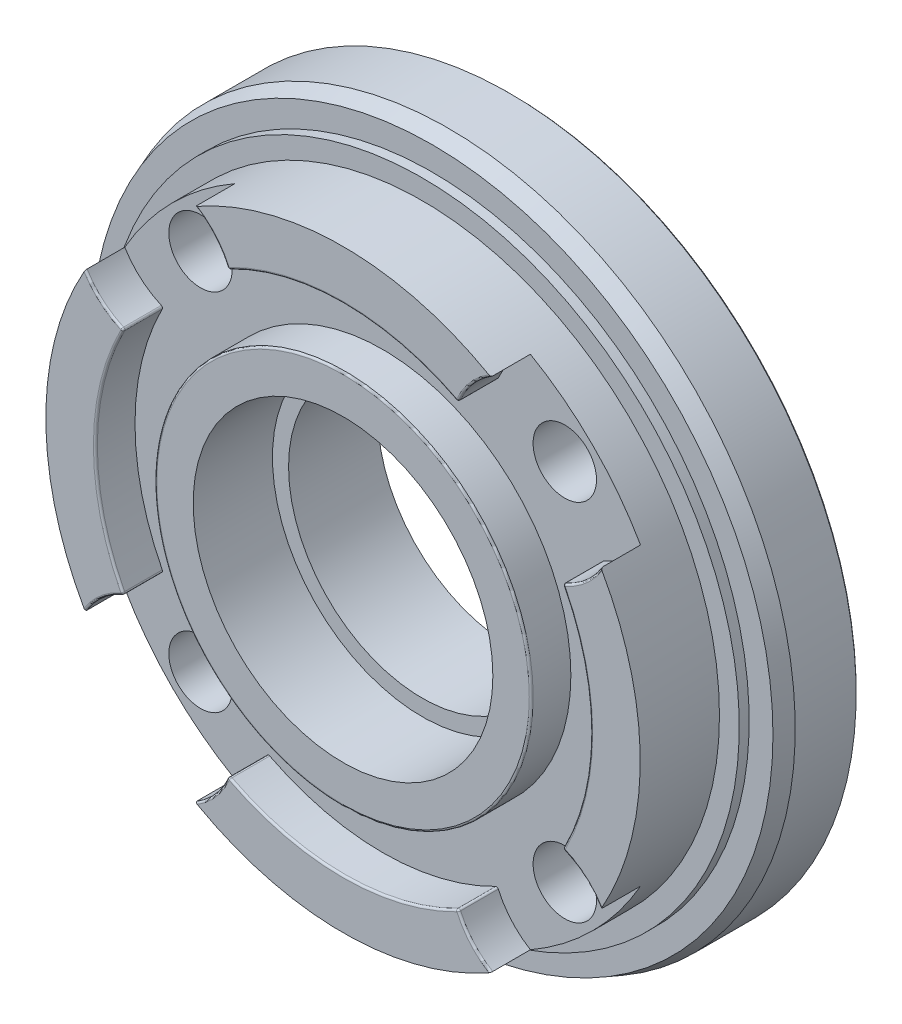
SolidWorks part; units mm, degrees
material "ABS"
ref_plane "Front Plane" through (0, 0, 0) normal (0, 0, 1) x (1, 0, 0)
ref_plane "Top Plane" through (0, 0, 0) normal (0, 1, 0) x (1, 0, 0)
ref_plane "Right Plane" through (0, 0, 0) normal (1, 0, 0) x (0, 0, -1)
sketch "Sketch1" plane through (0, 0, 0) normal (0, 0, 1) x (1, 0, 0)
  line L0 (0, 0) -> (13.5, 0) construction
  line L1 (0, 0) -> (9.5459, 9.5459) construction
  circle A0 centre (0, 0) radius 9.5
  circle A1 centre (0, 0) radius 15
  arc A2 (-6.285, 11.9478) -> (-11.9478, 6.285) centre (0, 0) ccw construction
  arc A3 (7.4565, 13.0154) -> (5.7957, 11.0752) centre (9.5459, 9.5459) ccw
  arc A4 (13.0154, -7.4565) -> (11.0752, -5.7957) centre (9.5459, -9.5459) ccw
  arc A5 (-7.4565, -13.0154) -> (-5.7957, -11.0752) centre (-9.5459, -9.5459) ccw
  arc A6 (-13.0154, 7.4565) -> (-11.0752, 5.7957) centre (-9.5459, 9.5459) ccw
  arc A7 (-11.0752, 5.7957) -> (-11.0752, -5.7957) centre (0, 0) ccw
  arc A8 (11.9478, 6.285) -> (6.285, 11.9478) centre (0, 0) ccw construction
  arc A9 (6.285, -11.9478) -> (11.9478, -6.285) centre (0, 0) ccw construction
  arc A10 (-11.9478, -6.285) -> (-6.285, -11.9478) centre (0, 0) ccw construction
  arc A11 (5.7957, 11.0752) -> (-5.7957, 11.0752) centre (0, 0) ccw
  arc A12 (-5.7957, -11.0752) -> (5.7957, -11.0752) centre (0, 0) ccw
  arc A13 (11.0752, -5.7957) -> (11.0752, 5.7957) centre (0, 0) ccw
  arc A14 (-5.7957, 11.0752) -> (-7.4565, 13.0154) centre (-9.5459, 9.5459) ccw
  arc A15 (11.0752, 5.7957) -> (13.0154, 7.4565) centre (9.5459, 9.5459) ccw
  arc A16 (5.7957, -11.0752) -> (7.4565, -13.0154) centre (9.5459, -9.5459) ccw
  arc A17 (-11.0752, -5.7957) -> (-13.0154, -7.4565) centre (-9.5459, -9.5459) ccw
  circle A18 centre (0, 0) radius 7.5625
  point P17 (0, 0)
  dimension "D1" = 19
  dimension "D2" = 30
  dimension "D3" = 27
  dimension "D4" = 45
  dimension "D5" = 8.1
  dimension "D6" = 4
  dimension "D7" = 25
  dimension "D8" = 15.125
extrude "Boss-Extrude1" add sketch "Sketch1" along normal blind 2 contours A14 A11 A3 A1 | A15 A13 A4 A1 | A16 A12 A5 A1 | A17 A7 A6 A1 | A0 A18 region at (-9.2313, 0, 0) region at (13.2504, 0, 0) region at (0, 13.2504, 0) region at (0, -13.2504, 0) region at (-13.2504, 0, 0)
sketch "Sketch2" plane through (0, 0, 0) normal (0, 0, 1) x (1, 0, 0)
  circle A0 centre (0, 0) radius 15
extrude "Boss-Extrude2" add sketch "Sketch2" against normal blind 2
fillet "Fillet1" radius 0.1 8 edges at (-5.7957, -11.0752, 1) (5.7957, -11.0752, 1) (11.0752, -5.7957, 1) (11.0752, 5.7957, 1) (5.7957, 11.0752, 1) (-5.7957, 11.0752, 1) (-11.0752, 5.7957, 1) (-11.0752, -5.7957, 1)
fillet "Fillet2" radius 0.1 21 edges at (6.5042, 12.2199, 2) (5.7793, 11.1194, 2) (-6.5042, 12.2199, 2) (-5.7793, 11.1194, 2) (12.2199, -6.5042, 2) (11.1194, -5.7793, 2) (12.2199, 6.5042, 2) (11.1194, 5.7793, 2) (-6.5042, -12.2199, 2) (-5.7793, -11.1194, 2) (6.5042, -12.2199, 2) (5.7793, -11.1194, 2) (-12.2199, 6.5042, 2) (-11.1194, 5.7793, 2) (-12.2199, -6.5042, 2) (-11.1194, -5.7793, 2) (0, 12.5, 2) (12.5, 0, 2) (0, -12.5, 2) (9.5, 0, 2) (-12.5, 0, 2)
sketch "Sketch3" plane through (0, 0, -2) normal (0, 0, -1) x (-1, 0, 0)
  line L1 (9.1924, 9.1924) -> (-9.1924, 9.1924) construction
  line L2 (-9.1924, 9.1924) -> (-9.1924, -9.1924) construction
  line L3 (-9.1924, -9.1924) -> (9.1924, -9.1924) construction
  line L4 (9.1924, -9.1924) -> (9.1924, 9.1924) construction
  circle A0 centre (0, 0) radius 13 construction
  circle A1 centre (-9.1924, 9.1924) radius 1.6
  circle A2 centre (9.1924, 9.1924) radius 1.6
  circle A3 centre (9.1924, -9.1924) radius 1.6
  circle A4 centre (-9.1924, -9.1924) radius 1.6
  point P17 (0, 0)
  dimension "D1" = 26
  dimension "D2" = 3.2
  dimension "D3" = 4
sketch "Sketch4" plane through (0, 0, -2) normal (0, 0, -1) x (-1, 0, 0)
  circle A0 centre (0, 0) radius 16
  dimension "D1" = 32
extrude "Boss-Extrude3" add sketch "Sketch4" along normal blind 0.5
sketch "Sketch5" plane through (0, 0, -2.5) normal (0, 0, -1) x (-1, 0, 0)
  circle A0 centre (0, 0) radius 17.5
  dimension "D1" = 35
extrude "Boss-Extrude4" add sketch "Sketch5" along normal blind 4
extrude "Cut-Extrude2" cut sketch "Sketch3" against normal through all and the other way through all
sketch "Sketch6" plane through (0, 0, -6.5) normal (0, 0, -1) x (-1, 0, 0)
  circle A0 centre (-9.1924, 9.1924) radius 2.1
  circle A1 centre (9.1924, 9.1924) radius 2.1
  circle A2 centre (9.1924, -9.1924) radius 2.1
  circle A3 centre (-9.1924, -9.1924) radius 2.1
  point P12 (0, 0)
  dimension "D1" = 4.2
  dimension "D2" = 4
extrude "Cut-Extrude3" cut sketch "Sketch6" against normal blind 4
sketch "Sketch7" plane through (0, 0, -6.5) normal (0, 0, -1) x (-1, 0, 0)
  line L0 (0, 0) -> (0, 13) construction
  line L1 (0, 13) -> (-13, 0) construction
  line L2 (-13, 0) -> (0, -13) construction
  line L3 (0, -13) -> (13, 0) construction
  line L4 (13, 0) -> (0, 13) construction
  circle A0 centre (0, 0) radius 13 construction
  circle A1 centre (0, 13) radius 2.6
  circle A2 centre (13, 0) radius 2.6
  circle A3 centre (0, -13) radius 2.6
  circle A4 centre (-13, 0) radius 2.6
  point P17 (0, 0)
  dimension "D1" = 26
  dimension "D2" = 5.2
  dimension "D3" = 4
extrude "Cut-Extrude4" cut sketch "Sketch7" against normal blind 4
sketch "Sketch8" plane through (0, 0, 0) normal (0, 0, 1) x (1, 0, 0)
  circle A0 centre (0, 0) radius 6.75
  dimension "D1" = 13.5
extrude "Middle Cutout" cut sketch "Sketch8" against normal blind 7
chamfer "Chamfer1" distance 0.1 angle 45 1 edges at (-17.5, 0, -6.5)
sketch "Sketch9" plane through (0, 0, 0) normal (0, 0, 1) x (1, 0, 0)
  circle A0 centre (0, 0) radius 7.5625
  dimension "D1" = 15.125
extrude "Cut-Extrude6" cut sketch "Sketch9" against normal blind 2
chamfer "Chamfer2" distance 0.3 angle 70 1 edges at (-17.5, 0, -2.5) first distance on face at (-16, 0, -2.5)
equation "\"RingPinShaft\"= 5.05"
equation "\"CenterBearingOut\"=32.05"
equation "\"OutputBearingOut\"=37.05"
equation "\"RingPostIn\"=5.15"
equation "\"CamBearingOut\"=15.1"
equation "\"DiskOutputShaft\"=10.1"
equation "\"CenterShaft\"=25.2"
equation "\"Eccentricity\"=2"
equation "\"CycCamShaft\"=10.05"
equation "\"m3Thru\"=3.15"
equation "\"m3Insert\"=4.2"
equation "\"D1@Sketch6\"=\"m3Insert\""
